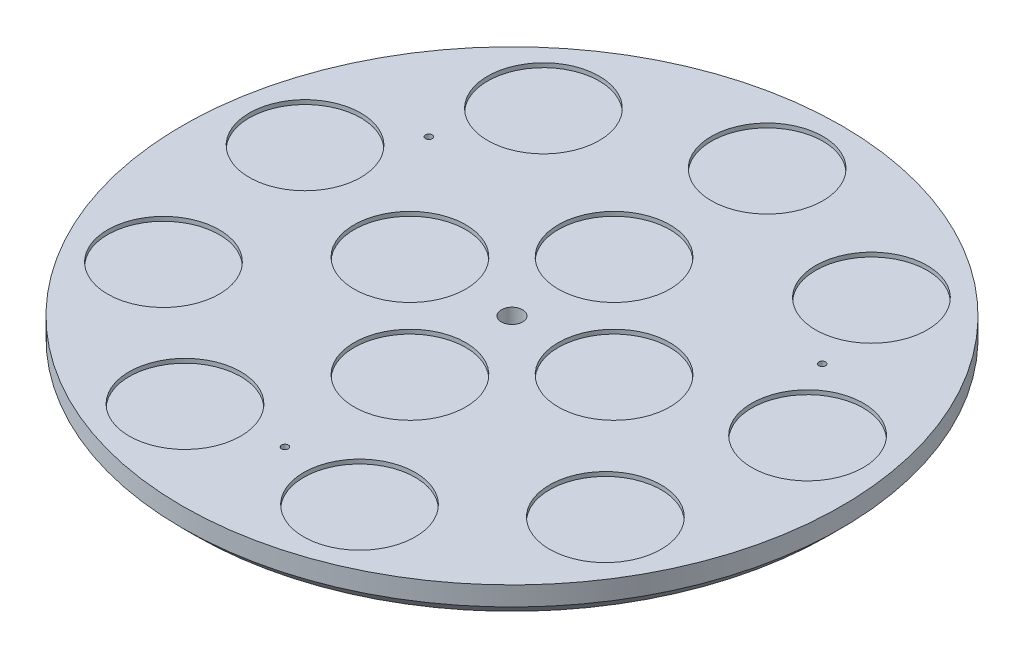
SolidWorks part; units mm, degrees
ref_plane "Plan de face" through (0, 0, 0) normal (0, 0, 1) x (1, 0, 0)
ref_plane "Plan de dessus" through (0, 0, 0) normal (0, 1, 0) x (1, 0, 0)
ref_plane "Plan de droite" through (0, 0, 0) normal (1, 0, 0) x (0, 0, -1)
sketch "Esquisse1" plane through (0, 0, 0) normal (0, 1, 0) x (1, 0, 0)
  circle A0 centre (0, 0) radius 155
  dimension "D1" = 310
extrude "Boss.-Extru.1" add sketch "Esquisse1" along normal blind 15
sketch "Esquisse2" plane through (0, 0, 0) normal (0, -1, 0) x (1, 0, 0)
  circle A0 centre (0, 0) radius 110.25
  dimension "D1" = 220.5
extrude "Enlèv. mat.-Extru.1" cut sketch "Esquisse2" against normal blind 2
sketch "Esquisse3" plane through (0, 2, 0) normal (0, -1, 0) x (-1, 0, 0)
  line L0 (0, 0) -> (0, -110.25) construction
  circle A0 centre (0, 0) radius 110.25 construction
  circle A1 centre (0, -106.8) radius 1.6
  dimension "D1" = 3.2
  dimension "D2" = 106.8
extrude "Enlèv. mat.-Extru.2" cut sketch "Esquisse3" against normal through all
pattern_circular "Répétition circulaire1" count 3 over 360 about axis through (0, 0, 0) along (0, -1, 0) of "Enlèv. mat.-Extru.2"
sketch "Esquisse4" plane through (0, 2, 0) normal (0, -1, 0) x (1, 0, 0)
  circle A0 centre (0, 0) radius 1
  dimension "D1" = 2
extrude "Enlèv. mat.-Extru.3" cut sketch "Esquisse4" against normal through all
sketch "Esquisse10" plane through (0, 15, 0) normal (0, 1, 0) x (1, 0, 0)
  circle A0 centre (0, 0) radius 5
  dimension "D1" = 10
extrude "Enlèv. mat.-Extru.6" cut sketch "Esquisse10" against normal offset from surface (11 mm away) 2 up to face at (0, 2, -1)
sketch "Esquisse8" plane through (0, 15, 0) normal (0, 1, 0) x (1, 0, 0)
  line L0 (0, 120) -> (0, 0) construction
  circle A0 centre (0, 120) radius 26.25
  circle A1 centre (0, 120) radius 33.5 construction
  point P20 (0, 0)
  dimension "D1" = 52.5
  dimension "D2" = 67
  dimension "D3" = 120
extrude "Enlèv. mat.-Extru.4" cut sketch "Esquisse8" against normal blind 2
pattern_circular "Répétition circulaire2" count 9 over 360 about axis through (0, 15, 0) along (0, 1, 0) of "Enlèv. mat.-Extru.4"
sketch "Esquisse9" plane through (0, 15, 0) normal (0, 1, 0) x (1, 0, 0)
  line L0 (0, 48) -> (0, 0) construction
  circle A0 centre (0, 48) radius 26.25
  circle A1 centre (0, 48) radius 33.5 construction
  dimension "D1" = 52.5
  dimension "D2" = 67
  dimension "D3" = 48
extrude "Enlèv. mat.-Extru.5" cut sketch "Esquisse9" against normal blind 2
pattern_circular "Répétition circulaire3" count 4 over 360 about axis through (0, 15, 0) along (0, 1, 0) of "Enlèv. mat.-Extru.5"
chamfer "Chanfrein1" distance 6 angle 45 1 edges at (0, 0, 155)
